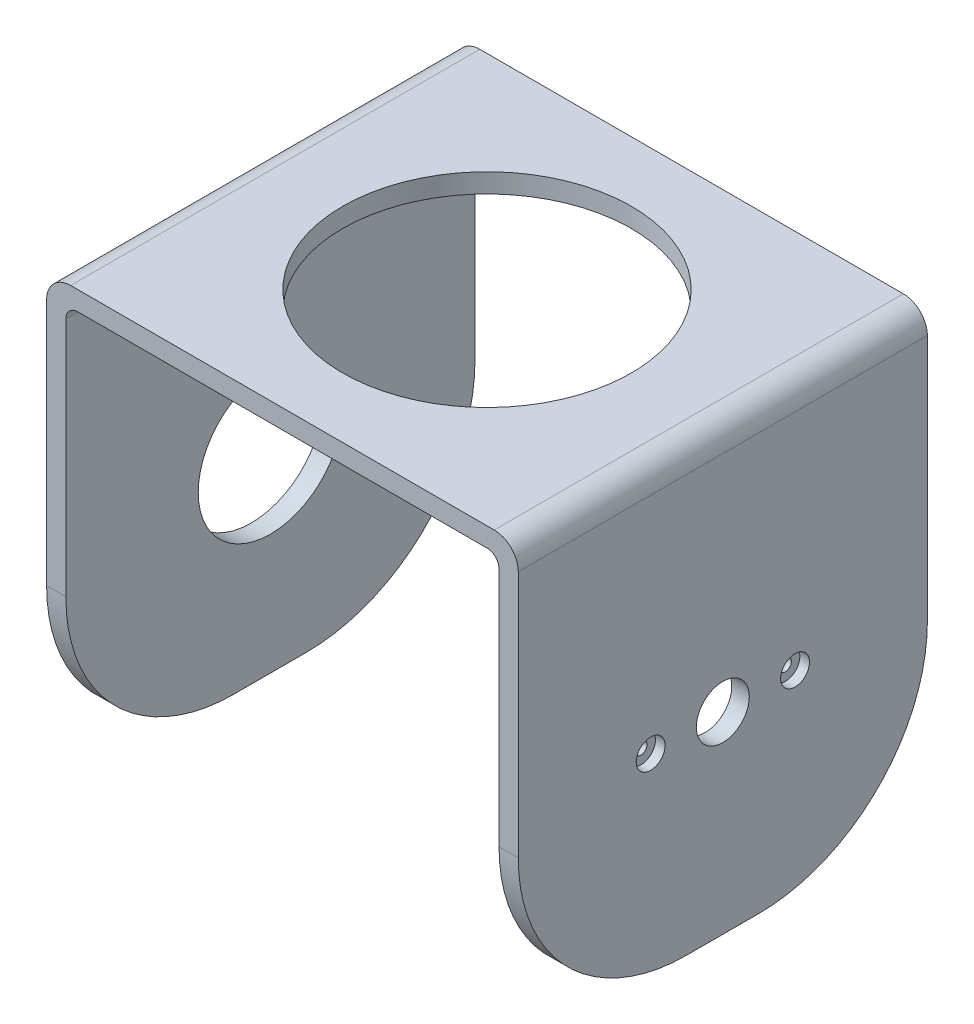
SolidWorks part; units mm, degrees
material "6061 合金"
ref_plane "前视基准面" through (0, 0, 0) normal (0, 0, 1) x (1, 0, 0)
ref_plane "上视基准面" through (0, 0, 0) normal (0, 1, 0) x (1, 0, 0)
ref_plane "右视基准面" through (0, 0, 0) normal (1, 0, 0) x (0, 0, -1)
other "Configuration Table"
sketch "草图1" plane through (0, 0, 0) normal (0, 0, 1) x (1, 0, 0)
  line L0 (-180, 0) -> (0, 0)
  line L1 (0, 0) -> (0, -175)
  line L3 (8, -175) -> (8, 8)
  line L4 (8, 8) -> (-180, 8)
  line L6 (0, -175) -> (8, -175)
  line L12 (-180, 8) -> (-188, 8)
  line L13 (-180, 0) -> (-180, -175)
  line L14 (-180, -175) -> (-188, -175)
  line L15 (-188, 8) -> (-188, -175)
  dimension "D1" = 8
  dimension "D2" = 8
  dimension "D4" = 180
  dimension "D5" = 183
  dimension "D6" = 8
  dimension "D8" = 8
extrude "凸台-拉伸1" add sketch "草图1" along normal blind 170
sketch "草图2" plane through (0, 8, 0) normal (0, 1, 0) x (1, 0, 0)
  line L0 (-216.3195, -85) -> (51.5119, -85) construction
  line L1 (8, -170) -> (-188, -170) construction
  line L2 (8, 0) -> (-188, 0) construction
  line L7 (-90, -75.3242) -> (-90, -92.2023) construction
  line L8 (8, -170) -> (8, 0) construction
  line L9 (-188, -170) -> (-188, 0) construction
  circle A2 centre (-90, -85) radius 60
  dimension "D3" = 120
extrude "切除-拉伸1" cut sketch "草图2" against normal blind 180 contours A2 L0 | L0 A2
sketch "草图3" plane through (8, 0, 0) normal (1, 0, 0) x (0, 0, -1)
  line L0 (-85, 25.6845) -> (-85, -173.3318) construction
  line L1 (0, -175) -> (0, 8) construction
  line L2 (-170, -175) -> (-170, 8) construction
  line L3 (-170, -175) -> (0, -175) construction
  line L4 (0, 0) -> (-209.686, 0) construction
  circle A0 centre (-85, -95) radius 11
  dimension "D1" = 22
  dimension "D2" = 80
extrude "切除-拉伸2" cut sketch "草图3" against normal through all both and the other way through all contours A0
fillet "圆角1" radius 70 4 edges at (-184, -175, 170) (-184, -175, 0) (4, -175, 0) (4, -175, 170)
fillet "圆角2" radius 5 2 edges at (-180, 0, 85) (0, 0, 85)
fillet "圆角3" radius 10 2 edges at (8, 8, 85) (-188, 8, 85)
sketch "草图6" plane through (-188, 0, 0) normal (-1, 0, 0) x (0, 0, 1)
  circle A0 centre (85, -95) radius 30
  dimension "D1" = 60
extrude "切除-拉伸6" cut sketch "草图6" against normal blind 39
sketch "草图7" plane through (0, 0, 0) normal (-1, 0, 0) x (0, 0, 1)
  circle A0 centre (85, -95) radius 13
  dimension "D1" = 26
extrude "切除-拉伸7" cut sketch "草图7" against normal blind 0.7
sketch "草图8" plane through (8, 0, 0) normal (1, 0, 0) x (0, 0, -1)
  line L0 (-85, -95) -> (-13.3452, -95) construction
  line L1 (-85, -95) -> (-143.0331, -95) construction
  circle A0 centre (-55, -95) radius 2.5
  circle A1 centre (-115, -95) radius 2.5
  dimension "D1" = 5
  dimension "D2" = 5
  dimension "D3" = 30
  dimension "D4" = 30
extrude "切除-拉伸8" cut sketch "草图8" against normal blind 10
sketch "草图9" plane through (8, 0, 0) normal (1, 0, 0) x (0, 0, -1)
  circle A0 centre (-55, -95) radius 6
  circle A1 centre (-115, -95) radius 6
  dimension "D1" = 12
  dimension "D2" = 12
extrude "切除-拉伸9" cut sketch "草图9" against normal blind 4
